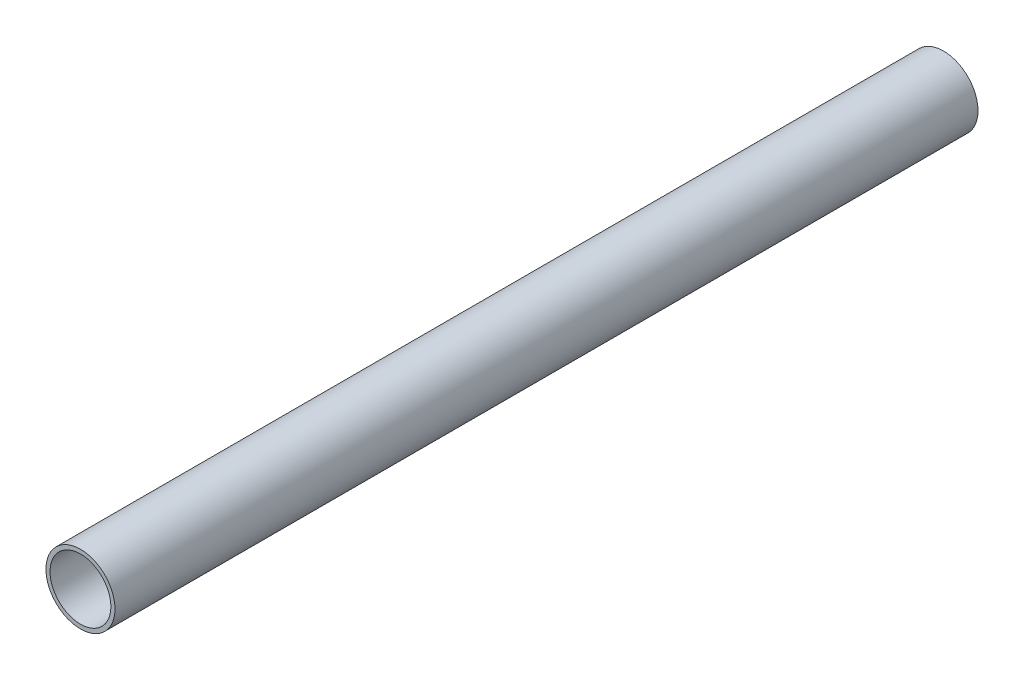
SolidWorks part; units mm, degrees
material "PE Высокой плотности"
ref_plane "Front" through (0, 0, 0) normal (0, 0, 1) x (1, 0, 0)
ref_plane "Top" through (0, 0, 0) normal (0, 1, 0) x (1, 0, 0)
ref_plane "Side" through (0, 0, 0) normal (1, 0, 0) x (0, 0, -1)
sketch "PipeSketch" plane through (0, 0, 0) normal (0, 0, 1) x (1, 0, 0)
  circle A0 centre (0, 0) radius 16
  circle A1 centre (0, 0) radius 14.1
  dimension "OuterDiameter" = 32
  dimension "InnerDiameter" = 28.2
extrude "Extrusion" add sketch "PipeSketch" along normal blind 400
sketch "FilterSketch" plane through (0, 0, 0) normal (0, 0, 1) x (1, 0, 0)
  circle A0 centre (0, 0) radius 16 construction
  dimension "NominalDiameter" = 32
